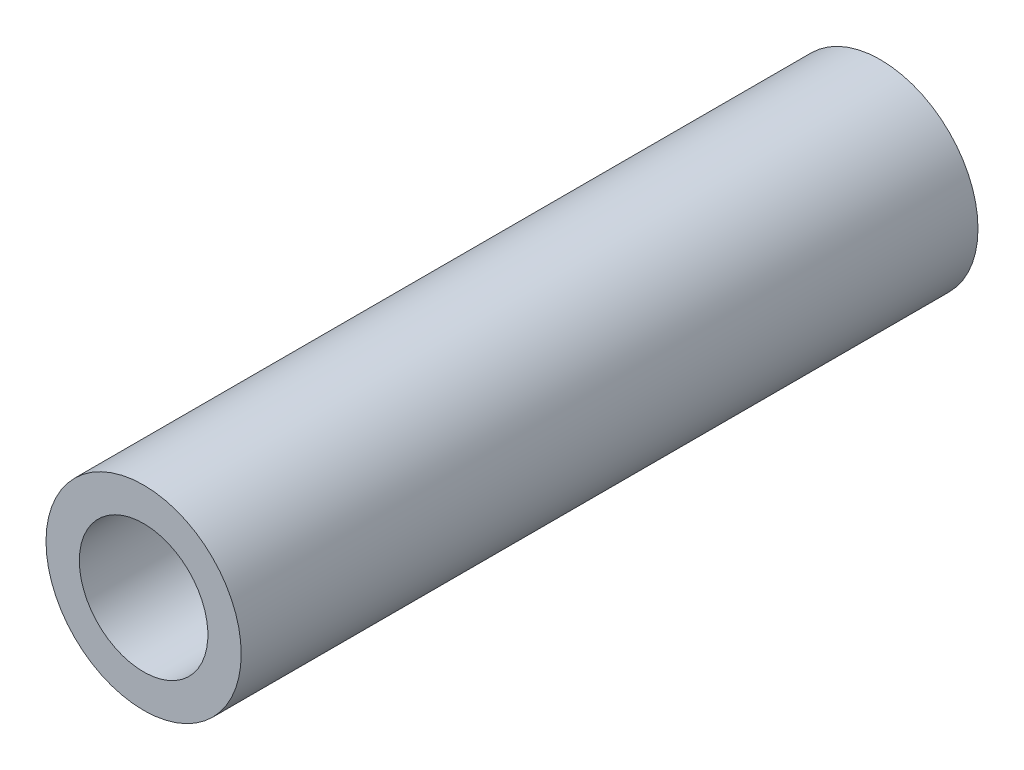
SolidWorks part; units mm, degrees
ref_plane "Front Plane" through (0, 0, 0) normal (0, 0, 1) x (1, 0, 0)
ref_plane "Top Plane" through (0, 0, 0) normal (0, 1, 0) x (1, 0, 0)
ref_plane "Right Plane" through (0, 0, 0) normal (1, 0, 0) x (0, 0, -1)
sketch "Sketch1" plane through (0, 0, 0) normal (0, 0, 1) x (1, 0, 0)
  circle A3 centre (59.4755, 35.57) radius 4.1
extrude "Boss-Extrude2" add sketch "Sketch1" along normal up to surface (30.95 mm away)
hole_wizard "M5 Clearance Hole1" positions "Sketch2" profile "Sketch3" hole size "M5" standard "ISO" end condition through all
sketch "Sketch2" plane through (0, 0, 0) normal (0, 0, -1) x (-1, 0, 0)
  point P0 (-59.4755, 35.57)
sketch "Sketch3" plane through (59.4755, 35.57, 0) normal (1, 0, 0) x (0, 1, 0)
  line L0 (0, 0) -> (0, 30.95)
  line L1 (0, 30.95) -> (2.7, 30.95)
  line L2 (2.7, 30.95) -> (2.7, 0)
  line L5 (2.7, 0) -> (0, 0)
  line L11 (0, -6.35) -> (0, 107.95) construction
  dimension "Thru Hole Dia." = 5.4
  dimension "Thru Hole Depth" = 30.95
